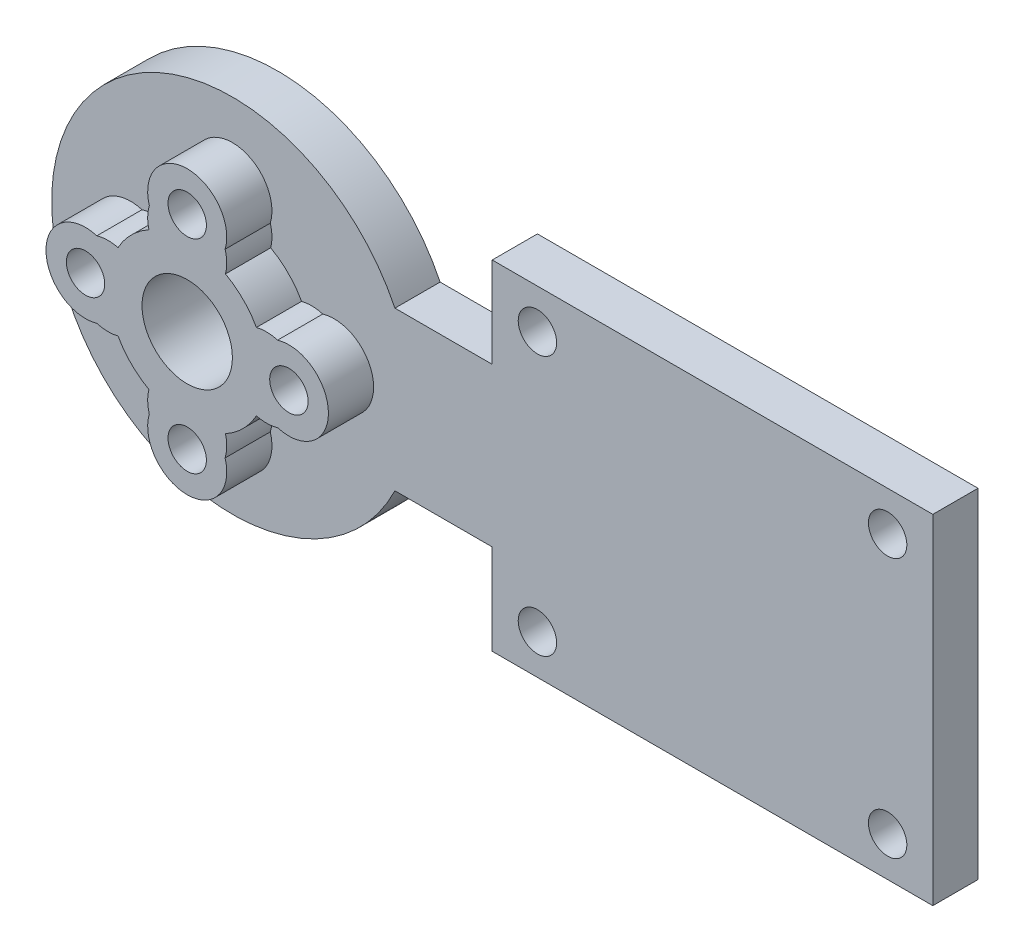
SolidWorks part; units mm, degrees
ref_plane "Front Plane" through (0, 0, 0) normal (0, 0, 1) x (1, 0, 0)
ref_plane "Top Plane" through (0, 0, 0) normal (0, 1, 0) x (1, 0, 0)
ref_plane "Right Plane" through (0, 0, 0) normal (1, 0, 0) x (0, 0, -1)
sketch "Metal_horn_flange_profile" plane through (0, 0, 0) normal (0, 0, 1) x (1, 0, 0)
  circle A0 centre (0, 0) radius 16
  dimension "D1" = 32
extrude "Metal_horn_flange" add sketch "Metal_horn_flange_profile" along normal blind 4
sketch "Straight_forearm_web_profile" plane through (0, 0, 0) normal (0, 0, 1) x (1, 0, 0)
  line L1 (0, -7) -> (28, -7)
  line L2 (0, -7) -> (0, 7)
  line L3 (0, 7) -> (28, 7)
  line L4 (28, -7) -> (28, 7)
  dimension "D1" = 28
  dimension "D2" = 14
  dimension "D3" = 7
extrude "Straight_forearm_web" add sketch "Straight_forearm_web_profile" along normal blind 4
sketch "Replaceable_tool_mounting_deck_profile" plane through (0, 0, 0) normal (0, 0, 1) x (1, 0, 0)
  line L1 (23, -15) -> (62, -15)
  line L2 (23, -15) -> (23, 15)
  line L3 (23, 15) -> (62, 15)
  line L4 (62, -15) -> (62, 15)
  dimension "D1" = 39
  dimension "D2" = 30
  dimension "D3" = 23
  dimension "D4" = 15
extrude "Replaceable_tool_mounting_deck" add sketch "Replaceable_tool_mounting_deck_profile" along normal blind 4
sketch "Dowel_support_hub_profile" plane through (0, 0, 0) normal (0, 0, 1) x (1, 0, 0)
  circle A0 centre (0, 0) radius 7
  circle A1 centre (0, 0) radius 4
  dimension "D1" = 14
  dimension "D2" = 8
extrude "Dowel_support_hub" add sketch "Dowel_support_hub_profile" along normal blind 4 from offset 4
sketch "Raised_washer_seats_PCD14" plane through (0, 0, 0) normal (0, 0, 1) x (1, 0, 0)
  circle A0 centre (7, 0) radius 3.5
  circle A1 centre (-7, 0) radius 3.5
  circle A2 centre (0, 7) radius 3.5
  circle A3 centre (0, -7) radius 3.5
  dimension "D1" = 7
  dimension "D2" = 7
  dimension "D3" = 7
  dimension "D4" = 7
  dimension "D5" = 7
  dimension "D6" = 7
  dimension "D7" = 7
  dimension "D8" = 7
extrude "Washer_seats_clear_dowel_sleeve" add sketch "Raised_washer_seats_PCD14" along normal blind 4 from offset 4
sketch "Metal_horn_M3_pattern_profile" plane through (0, 0, 0) normal (0, 0, 1) x (1, 0, 0)
  circle A0 centre (7, 0) radius 1.6
  circle A1 centre (-7, 0) radius 1.6
  circle A2 centre (0, 7) radius 1.6
  circle A3 centre (0, -7) radius 1.6
  dimension "D1" = 3.2
  dimension "D2" = 3.2
  dimension "D3" = 3.2
  dimension "D4" = 3.2
  dimension "D5" = 7
  dimension "D6" = 7
  dimension "D7" = 7
  dimension "D8" = 7
extrude "Metal_horn_M3_pattern_SUPERSEDED_owned_servo" [suppressed] cut sketch "Metal_horn_M3_pattern_profile" along normal through all from offset 50 offset against normal yes
sketch "Elbow_sleeve_bore_profile" plane through (0, 0, 0) normal (0, 0, 1) x (1, 0, 0)
  circle A0 centre (0, 0) radius 4
  dimension "D1" = 8
extrude "Elbow_sleeve_bore" cut sketch "Elbow_sleeve_bore_profile" along normal through all from offset 50 offset against normal yes
sketch "Modular_tool_four_M3_pattern_profile" plane through (0, 0, 0) normal (0, 0, 1) x (1, 0, 0)
  circle A0 centre (27, -11.5) radius 1.7
  circle A1 centre (27, 11.5) radius 1.7
  circle A2 centre (58, -11.5) radius 1.7
  circle A3 centre (58, 11.5) radius 1.7
  dimension "D1" = 3.4
  dimension "D2" = 3.4
  dimension "D3" = 3.4
  dimension "D4" = 3.4
  dimension "D5" = 27
  dimension "D6" = 58
  dimension "D7" = 11.5
  dimension "D8" = 11.5
extrude "Modular_tool_four_M3_pattern" cut sketch "Modular_tool_four_M3_pattern_profile" along normal through all from offset 50 offset against normal yes
sketch "Printed_hub_washer_seats_PCD18_profile" plane through (0, 0, 0) normal (0, 0, 1) x (1, 0, 0)
  circle A0 centre (9, 0) radius 3.5
  circle A1 centre (0, 9) radius 3.5
  circle A2 centre (-9, 0) radius 3.5
  circle A3 centre (0, -9) radius 3.5
  dimension "D1" = 7
  dimension "D2" = 7
  dimension "D3" = 7
  dimension "D4" = 7
extrude "Printed_hub_M3_washer_seats_PCD18" add sketch "Printed_hub_washer_seats_PCD18_profile" along normal blind 4 from offset 4
sketch "Printed_hub_M3_clearance_PCD18_profile" plane through (0, 0, 0) normal (0, 0, 1) x (1, 0, 0)
  circle A0 centre (9, 0) radius 1.7
  circle A1 centre (0, 9) radius 1.7
  circle A2 centre (-9, 0) radius 1.7
  circle A3 centre (0, -9) radius 1.7
  dimension "D1" = 3.4
  dimension "D2" = 3.4
  dimension "D3" = 3.4
  dimension "D4" = 3.4
extrude "Printed_hub_M3_clearance_PCD18" cut sketch "Printed_hub_M3_clearance_PCD18_profile" along normal through all from offset 50 offset against normal yes
